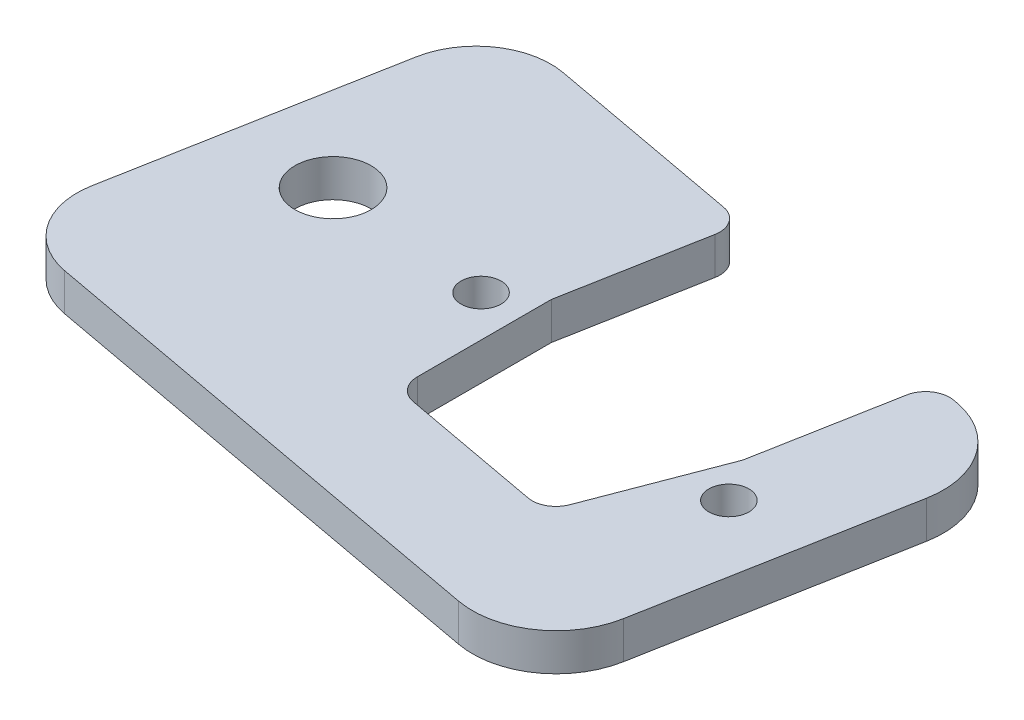
SolidWorks part; units mm, degrees
ref_plane "Front Plane" through (0, 0, 0) normal (0, 0, 1) x (1, 0, 0)
ref_plane "Top Plane" through (0, 0, 0) normal (0, 1, 0) x (1, 0, 0)
ref_plane "Right Plane" through (0, 0, 0) normal (1, 0, 0) x (0, 0, -1)
sketch "Sketch1" plane through (0, 0, 0) normal (0, 1, 0) x (1, 0, 0)
  line L0 (-26.3858, 2.6924) -> (-9.6505, -0.397)
  line L1 (-8.5253, -27.8933) -> (3.4348, -30.1012)
  line L2 (5.7017, -28.8285) -> (9.7689, -18.1881)
  line L3 (14.3033, -4.8191) -> (14.678, -4.8883)
  line L4 (20.3807, -13.1732) -> (16.3621, -34.9415)
  line L5 (8.0771, -40.6442) -> (-32.9866, -33.0635)
  line L6 (-38.0783, -25.6662) -> (-33.783, -2.3993)
  line L7 (-8.0212, -2.7641) -> (-10.1884, -14.5038)
  line L8 (14.4591, -30.4187) -> (17.2319, -15.399) construction
  line L9 (11.92, -6.5359) -> (9.7689, -18.1881) construction
  line L10 (-10.1884, -14.5038) -> (-10.1884, -25.8951)
  line L11 (9.7689, -18.1881) -> (11.9362, -6.4484)
  line L12 (9.7689, -18.1881) -> (5.7281, -28.7594) construction
  line L13 (-10.1884, -25.8211) -> (-10.1884, -14.5038) construction
  line L14 (-35.9307, -14.0327) -> (-27.6879, -15.5544) construction
  line L18 (-10.1884, -14.5038) -> (-8.0373, -2.8516) construction
  line L19 (-11.8691, -34.5211) -> (4.1917, -37.486) construction
  arc A0 (1.6614, -27.6171) -> (5.7281, -28.7594) centre (3.747, -28.0021) ccw construction
  arc A1 (-9.6505, -0.397) -> (-8.0212, -2.7641) centre (-10.0194, -2.3953) cw
  arc A2 (11.9362, -6.4484) -> (14.3033, -4.8191) centre (13.9344, -6.8173) cw
  arc A3 (-8.5253, -27.8933) -> (-10.1884, -25.8951) centre (-8.1564, -25.8951) cw
  arc A4 (3.4348, -30.1012) -> (5.7017, -28.8285) centre (3.8037, -28.103) ccw
  arc A5 (14.678, -4.8883) -> (20.3807, -13.1732) centre (13.3869, -11.8821) cw
  arc A6 (16.3621, -34.9415) -> (8.0771, -40.6442) centre (9.3683, -33.6504) cw
  circle A7 centre (12.1459, -21.7522) radius 1.7018
  circle A8 centre (-13.6813, -16.9843) radius 1.7018
  arc A9 (14.3907, -4.8352) -> (11.92, -6.5359) centre (14.0057, -6.9209) ccw construction
  circle A10 centre (-13.6813, -16.9843) radius 1.7018 construction
  arc A11 (-32.9866, -33.0635) -> (-38.0783, -25.6662) centre (-31.8338, -26.819) cw
  arc A12 (-26.3858, 2.6924) -> (-33.783, -2.3993) centre (-27.5385, -3.5521) ccw
  circle A13 centre (12.1459, -21.7522) radius 1.7018 construction
  circle A14 centre (-27.6879, -15.5544) radius 3.2385
  spline S0 degree 3 poles (-9.738, -0.3809) (-13.0249, 0.2259) (-15.7225, -6.8445) (-16.1636, -9.2339) knots 0 0 0 0 1 1 1 1 construction
  dimension "D2" = 2.032
  dimension "D1" = 2.032
  dimension "D4" = 7.112
  dimension "D5" = 7.112
  dimension "D6" = 9.525
  dimension "D7" = 6.35
  dimension "D9" = 6.477
  dimension "D3" = 9.525
  dimension "D8" = 25.4
  dimension "D10" = 8.382
extrude "Boss-Extrude1" add sketch "Sketch1" along normal blind 3.175
